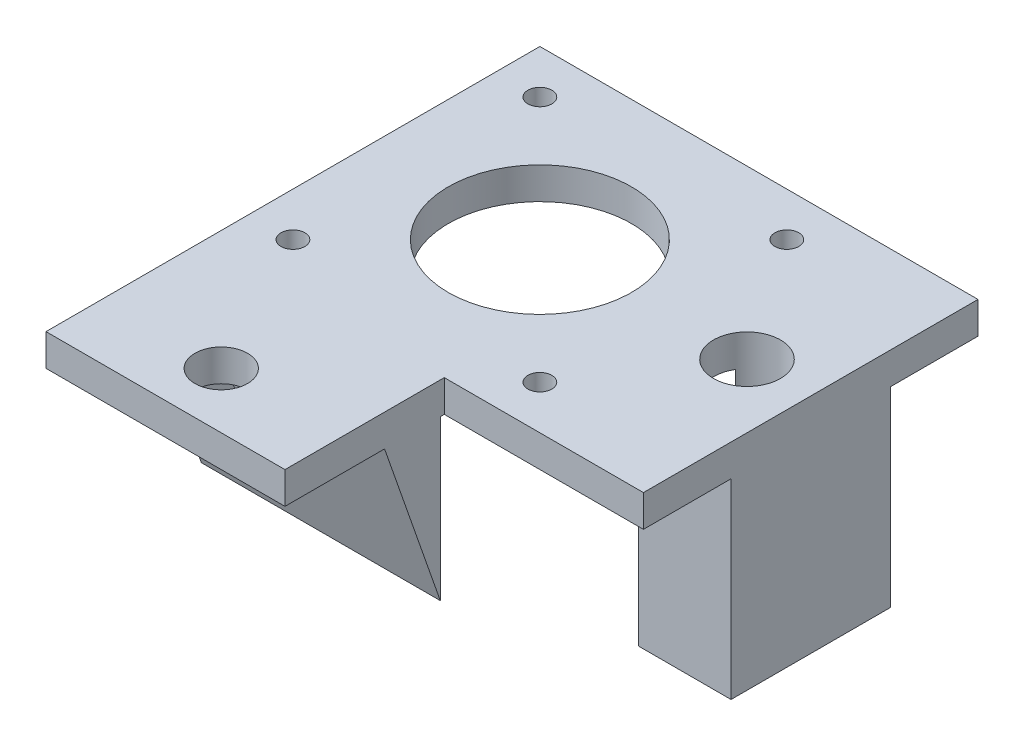
SolidWorks part; units mm, degrees
ref_plane "Front Plane" through (0, 0, 0) normal (0, 0, 1) x (1, 0, 0)
ref_plane "Top Plane" through (0, 0, 0) normal (0, 1, 0) x (1, 0, 0)
ref_plane "Right Plane" through (0, 0, 0) normal (1, 0, 0) x (0, 0, -1)
sketch "Sketch1" plane through (0, 0, 0) normal (0, 1, 0) x (1, 0, 0)
  line L0 (0, 21) -> (55, 21) construction
  line L2 (0, 0) -> (0, 42)
  line L3 (0, 42) -> (55, 42)
  line L4 (55, 0) -> (55, 42)
  line L5 (21, 42) -> (21, 0) construction
  line L6 (0, 0) -> (0, -20)
  line L7 (0, -20) -> (30, -20)
  line L8 (30, -20) -> (30, 0)
  line L9 (15, -20) -> (15, 0) construction
  line L13 (30, 0) -> (55, 0)
  line L14 (30, 0) -> (0, 0) construction
  circle A0 centre (47, 21) radius 4.2
  circle A1 centre (21, 21) radius 11.5
  circle A2 centre (5.5, 36.5) radius 1.5
  circle A3 centre (36.5, 36.5) radius 1.5
  circle A4 centre (5.5, 5.5) radius 1.5
  circle A5 centre (36.5, 5.5) radius 1.5
  circle A6 centre (15, -13) radius 3.3
  point P8 (55, 21)
  dimension "D2" = 23
  dimension "D4" = 8.4
  dimension "D9" = 3
  dimension "D13" = 6.6
  dimension "D1" = 26
  dimension "D3" = 42
  dimension "D5" = 21
  dimension "D6" = 55
  dimension "D7" = 15.5
  dimension "D8" = 15.5
  dimension "D10" = 30
  dimension "D11" = 20
  dimension "D12" = 13
extrude "Boss-Extrude1" add sketch "Sketch1" along normal blind 4
sketch "Sketch2" plane through (0, 0, 0) normal (0, -1, 0) x (1, 0, 0)
  line L1 (40.4, 0) -> (43.4, 0)
  line L2 (40.4, 0) -> (40.4, -42)
  line L3 (40.4, -42) -> (43.4, -42)
  line L4 (43.4, 0) -> (43.4, -42)
  line L5 (55, -42) -> (0, -42) construction
  line L6 (55, 0) -> (55, -42) construction
  line L7 (55, -11) -> (43.4, -11)
  line L8 (55, -11) -> (55, -31)
  line L9 (55, -31) -> (43.4, -31)
  line L10 (43.4, -11) -> (43.4, -31)
  line L11 (30, 0) -> (55, 0) construction
  circle A0 centre (47, -21) radius 6.6
  circle A1 centre (47, -21) radius 4.2
  circle A2 centre (47, -21) radius 4.2 construction
  point P25 (55, -21)
  point P26 (55, -21)
  circle M7 centre (47, -21) radius 4.2
  line M10 (55, -42) -> (55, 0)
  dimension "D1" = 2.4
  dimension "D2" = 3
  dimension "D3" = 20
extrude "Boss-Extrude2" add sketch "Sketch2" along normal blind 20 contours L4 A0 L10 M7 | A0 L10 L9 L7 L4 M10 region at (49.2, 0, -11.2312) region at (50.0669, 0, -15.3449)
sketch "Sketch3" plane through (0, -20, 0) normal (0, -1, 0) x (1, 0, 0)
  line L1 (55, -31) -> (43.4, -31)
  line L2 (55, -31) -> (55, -11)
  line L3 (55, -11) -> (43.4, -11)
  line L4 (43.4, -31) -> (43.4, -11)
extrude "Boss-Extrude3" add sketch "Sketch3" along normal blind 4
sketch "Sketch4" plane through (0, 0, 0) normal (-1, 0, 0) x (0, 0, 1)
  line L0 (-42, 0) -> (0.5, 0) construction
  line L1 (-42, 0) -> (20, 0) construction
  line L2 (0.5, 0) -> (7.5, 0)
  line L3 (7.5, 0) -> (0.5, -20)
  line L4 (0.5, -20) -> (0.5, 0)
  dimension "D1" = 42.5
  dimension "D2" = 7
  dimension "D3" = 20
extrude "Boss-Extrude4" add sketch "Sketch4" against normal up to surface (30 mm away) up to face at (30, 2, 10)
sketch "Sketch5" plane through (0, 0, 0) normal (0, -1, 0) x (1, 0, 0)
  circle A0 centre (15, 13) radius 8.75
  dimension "D1" = 17.5
extrude "Cut-Extrude1" cut sketch "Sketch5" along normal through all
equation "\"8mm hole\" = 8.4mm"
equation "\"22mm hole\"= 23mm"
equation "\"D2@Sketch1\"=\"22mm hole\""
equation "\"D4@Sketch1\"=\"8mm hole\""
equation "\"15mm hole\"= 15.8mm"
equation "\"D1@Sketch3\"= \"8mm hole\""
equation "\"bed height offset\"= 3mm"
equation "\"motor width\"= 42.5mm"
equation "\"D1@Sketch4\"= \"motor width\""
